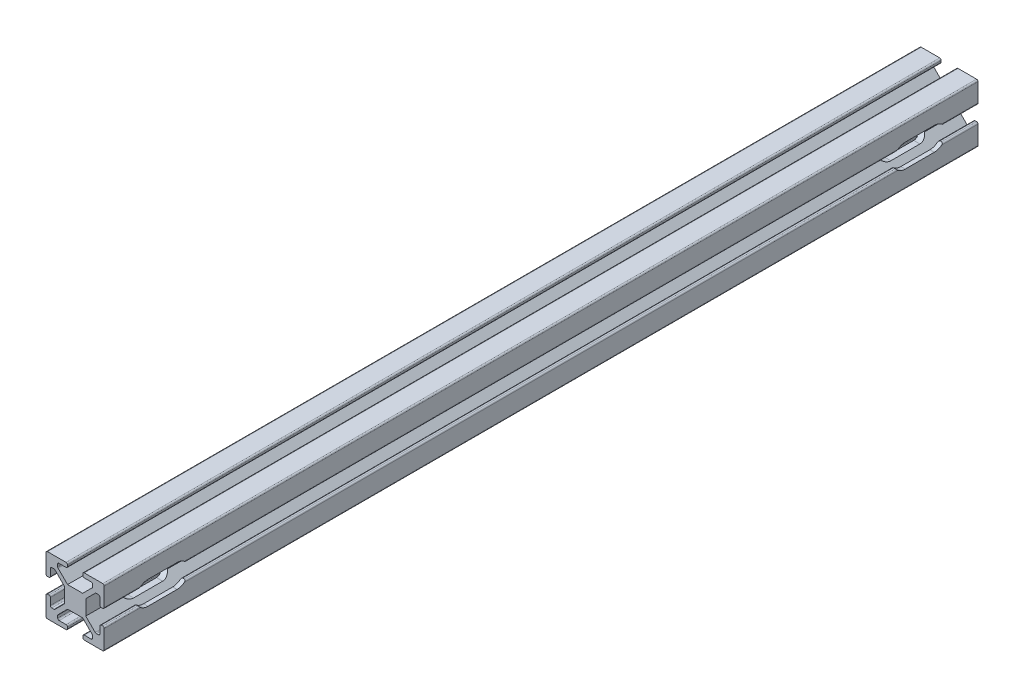
SolidWorks part; units mm, degrees
material "6061 Alloy"
ref_plane "Front Plane" through (0, 0, 0) normal (0, 0, 1) x (1, 0, 0)
ref_plane "Top Plane" through (0, 0, 0) normal (0, 1, 0) x (1, 0, 0)
ref_plane "Right Plane" through (0, 0, 0) normal (1, 0, 0) x (0, 0, -1)
sketch "Sketch1" plane through (0, 0, 0) normal (0, 0, 1) x (1, 0, 0)
  line L0 (-10, 2.63) -> (-10, 10)
  line L1 (-10, 10) -> (-2.63, 10)
  line L2 (-2.63, 10) -> (-2.63, 8.5)
  line L3 (-2.63, 8.5) -> (-5.995, 8.5)
  line L4 (-5.995, 8.5) -> (-5.995, 7.0557)
  line L5 (-5.995, 7.0557) -> (-2.5943, 3.655)
  line L6 (-2.5943, 3.655) -> (2.5943, 3.655)
  line L7 (0, 3.655) -> (0, 0) construction
  line L8 (0, 0) -> (-3.655, 0) construction
  line L9 (-3.655, -2.5943) -> (-3.655, 2.5943)
  line L10 (-3.655, 2.5943) -> (-7.0557, 5.995)
  line L11 (-7.0557, 5.995) -> (-8.5, 5.995)
  line L12 (-8.5, 5.995) -> (-8.5, 2.63)
  line L13 (-8.5, 2.63) -> (-10, 2.63)
  line L14 (8.5, 2.63) -> (10, 2.63)
  line L15 (8.5, 5.995) -> (8.5, 2.63)
  line L16 (7.0557, 5.995) -> (8.5, 5.995)
  line L17 (3.655, 2.5943) -> (7.0557, 5.995)
  line L18 (3.655, -2.5943) -> (3.655, 2.5943)
  line L19 (5.995, 7.0557) -> (2.5943, 3.655)
  line L20 (5.995, 8.5) -> (5.995, 7.0557)
  line L21 (2.63, 8.5) -> (5.995, 8.5)
  line L22 (2.63, 10) -> (2.63, 8.5)
  line L23 (10, 10) -> (2.63, 10)
  line L24 (10, 2.63) -> (10, 10)
  line L25 (10, -2.63) -> (10, -10)
  line L26 (10, -10) -> (2.63, -10)
  line L27 (2.63, -10) -> (2.63, -8.5)
  line L28 (2.63, -8.5) -> (5.995, -8.5)
  line L29 (5.995, -8.5) -> (5.995, -7.0557)
  line L30 (5.995, -7.0557) -> (2.5943, -3.655)
  line L31 (3.655, -2.5943) -> (7.0557, -5.995)
  line L32 (7.0557, -5.995) -> (8.5, -5.995)
  line L33 (8.5, -5.995) -> (8.5, -2.63)
  line L34 (8.5, -2.63) -> (10, -2.63)
  line L35 (-8.5, -2.63) -> (-10, -2.63)
  line L36 (-8.5, -5.995) -> (-8.5, -2.63)
  line L37 (-7.0557, -5.995) -> (-8.5, -5.995)
  line L38 (-3.655, -2.5943) -> (-7.0557, -5.995)
  line L39 (-2.5943, -3.655) -> (2.5943, -3.655)
  line L40 (-5.995, -7.0557) -> (-2.5943, -3.655)
  line L41 (-5.995, -8.5) -> (-5.995, -7.0557)
  line L42 (-2.63, -8.5) -> (-5.995, -8.5)
  line L43 (-2.63, -10) -> (-2.63, -8.5)
  line L44 (-10, -10) -> (-2.63, -10)
  line L45 (-10, -2.63) -> (-10, -10)
  point P41 (3.655, 0)
  dimension "D1" = 20
  dimension "D2" = 20
  dimension "D3" = 5.26
  dimension "D4" = 11.99
  dimension "D5" = 1.5
  dimension "D6" = 1.5
  dimension "D7" = 7.31
extrude "Boss-Extrude1" add sketch "Sketch1" against normal blind 300
fillet "Fillet1" radius 0.5 36 edges at (10, 10, -150) (7.0557, 5.995, -150) (8.5, 2.63, -150) (10, 2.63, -150) (8.5, 5.995, -150) (2.63, 10, -150) (2.63, 8.5, -150) (5.995, 8.5, -150) (5.995, 7.0557, -150) (10, -10, -150) (10, -2.63, -150) (8.5, -2.63, -150) (8.5, -5.995, -150) (7.0557, -5.995, -150) (5.995, -7.0557, -150) (5.995, -8.5, -150) (2.63, -8.5, -150) (2.63, -10, -150) (-10, -10, -150) (-2.63, -10, -150) (-2.63, -8.5, -150) (-5.995, -8.5, -150) (-5.995, -7.0557, -150) (-7.0557, -5.995, -150) (-8.5, -5.995, -150) (-10, -2.63, -150) (-8.5, -2.63, -150) (-7.0557, 5.995, -150) (-10, 10, -150) (-10, 2.63, -150) (-8.5, 2.63, -150) (-8.5, 5.995, -150) (-5.995, 8.5, -150) (-5.995, 7.0557, -150) (-2.63, 8.5, -150) (-2.63, 10, -150)
sketch "Sketch2" plane through (0, 0, 0) normal (1, 0, 0) x (0, 0, -1)
  line L0 (150, 9.5) -> (150, -9.5) construction
  line L1 (300, 9.5) -> (0, 9.5) construction
  line L2 (0, -9.5) -> (300, -9.5) construction
  line L3 (15, 4) -> (25, 4)
  line L4 (15, -4) -> (25, -4)
  line L5 (285, 4) -> (275, 4)
  line L6 (285, -4) -> (275, -4)
  arc A0 (15, 4) -> (15, -4) centre (15, 0) ccw
  arc A2 (25, -4) -> (25, 4) centre (25, 0) ccw
  arc A3 (285, 4) -> (285, -4) centre (285, 0) cw
  arc A4 (275, -4) -> (275, 4) centre (275, 0) cw
  point P17 (0, 0)
  point P18 (0, 0)
  point P19 (0, 0)
  point P20 (30, 0)
  point P21 (30.5752, 4)
  dimension "D1" = 8
  dimension "D2" = 15
  dimension "D3" = 10
extrude "Cut-Extrude1" cut sketch "Sketch2" against normal through all both and the other way through all
